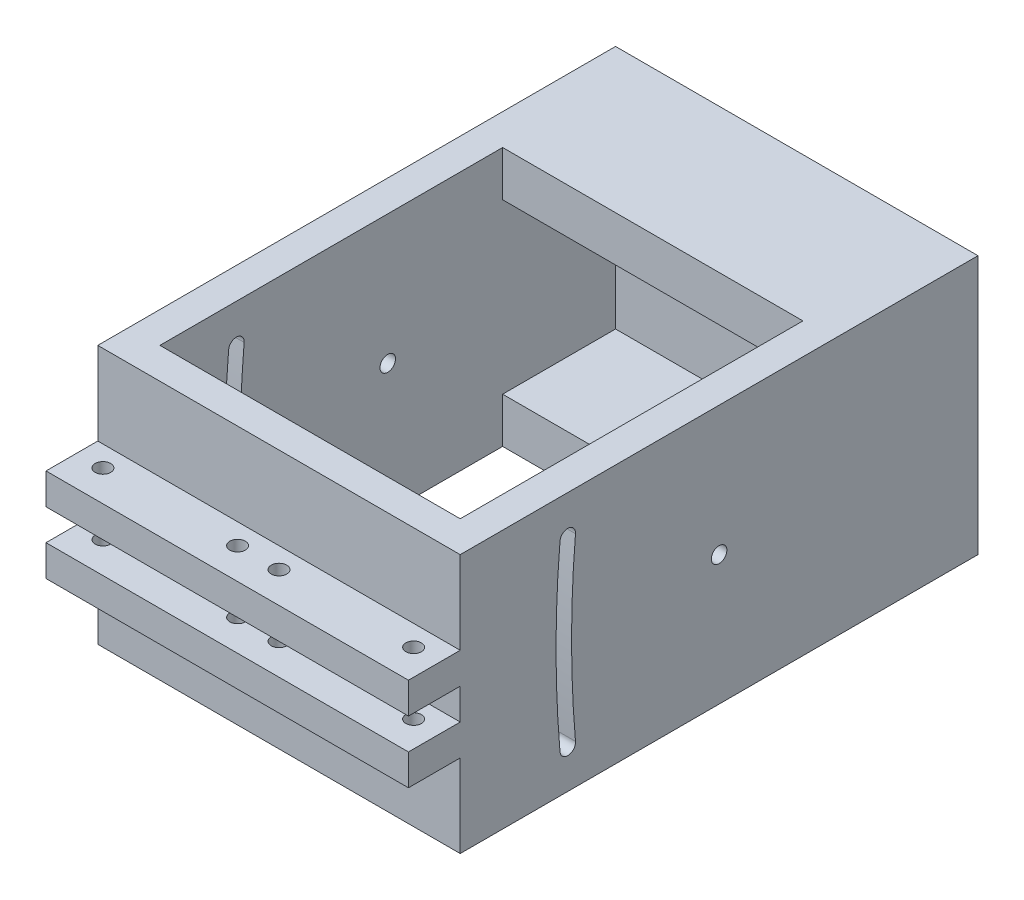
SolidWorks part; units mm, degrees
ref_plane "Front Plane" through (0, 0, 0) normal (0, 0, 1) x (1, 0, 0)
ref_plane "Top Plane" through (0, 0, 0) normal (0, 1, 0) x (1, 0, 0)
ref_plane "Right Plane" through (0, 0, 0) normal (1, 0, 0) x (0, 0, -1)
sketch "Sketch1" plane through (0, 0, 0) normal (0, 1, 0) x (1, 0, 0)
  line L1 (-35, 48.4099) -> (35, 48.4099)
  line L2 (-35, 48.4099) -> (-35, -51.5901)
  line L3 (-35, -51.5901) -> (35, -51.5901)
  line L4 (35, 48.4099) -> (35, -51.5901)
  line L14 (0, -27.5) -> (0, 27.5) construction
  line L16 (-29, 42.4099) -> (29, 42.4099)
  line L17 (-29, 42.4099) -> (-29, -45.5901)
  line L18 (-29, -45.5901) -> (29, -45.5901)
  line L19 (29, 42.4099) -> (29, -45.5901)
  point P14 (0, -51.5901)
  dimension "D1" = 70
  dimension "D2" = 100
  dimension "D3" = 6
  dimension "D4" = 6
  dimension "D5" = 6
  dimension "D6" = 6
  dimension "D9" = 0
extrude "main_body" add sketch "Sketch1" along normal blind 50
sketch "Sketch2" plane through (35, 0, 0) normal (1, 0, 0) x (0, 0, -1)
  line L0 (-51.5901, 50) -> (-51.5901, 0) construction
  circle A0 centre (-1.5901, 25) radius 1.5
  point P4 (-51.5901, 25)
  dimension "D1" = 3
  dimension "D2" = 0
  dimension "D3" = 50
sketch "Sketch3" plane through (0, 0, 51.5901) normal (0, 0, 1) x (1, 0, 0)
  line L0 (-35, 50) -> (35, 50) construction
  line L1 (35, 50) -> (35, 0) construction
  circle A0 centre (0, 25) radius 1.5
  point P4 (0, 50)
  point P7 (35, 25)
  dimension "D1" = 0
  dimension "D3" = 3
  dimension "D2" = 0
extrude "back_wire_hole" cut sketch "Sketch3" against normal up to next
sketch "Sketch6" plane through (0, 0, -48.4099) normal (0, 0, -1) x (-1, 0, 0)
  line L0 (35, 50) -> (35, 0) construction
  line L1 (-35, 50) -> (35, 50) construction
  circle A0 centre (0, 25) radius 1.5
  point P4 (35, 25)
  point P7 (0, 50)
  dimension "D1" = 0
  dimension "D3" = 3
  dimension "D2" = 0
extrude "front_wire_hole" cut sketch "Sketch6" against normal up to next
sketch "Sketch4" plane through (0, 0, 51.5901) normal (0, 0, 1) x (1, 0, 0)
  line L6 (-35, 50) -> (-35, 0) construction
  line L8 (-35, 34) -> (35, 34)
  line L10 (-35, 34) -> (-35, 28)
  line L12 (-35, 28) -> (35, 28)
  line L13 (35, 34) -> (35, 28)
  line L14 (35, 50) -> (35, 0) construction
  point P8 (-35, 25)
  dimension "D1" = 6
  dimension "D2" = 3
extrude "back_lip" add sketch "Sketch4" along normal blind 10
ref_plane "central_horizontal_plane" [suppressed] through (0, 25, 0) normal (0, 1, 0) x (1, 0, 0)
mirror "back_lip_mirror" about plane through (0, 25, 0) normal (0, 1, 0) of "back_lip"
sketch "Sketch5" plane through (0, 34, 0) normal (0, 1, 0) x (1, 0, 0)
  line L0 (35, -61.5901) -> (-35, -61.5901) construction
  line L1 (35, -51.5901) -> (-35, -51.5901) construction
  line L2 (35, -61.5901) -> (35, -51.5901) construction
  line L3 (0, -61.5901) -> (0, -51.5901) construction
  circle A0 centre (4, -55.5901) radius 1.5
  circle A1 centre (30, -55.5901) radius 1.5
  circle A2 centre (-30, -55.5901) radius 1.5
  circle A3 centre (-4, -55.5901) radius 1.5
  point P4 (0, -61.5901)
  dimension "D1" = 4
  dimension "D3" = 0
  dimension "D5" = 3
  dimension "D6" = 3
  dimension "D2" = 4
  dimension "D4" = 5
extrude "back_lip_holes" cut sketch "Sketch5" against normal through all
extrude "geared_arm_hole" cut sketch "Sketch2" against normal up to next
mirror "geared_arm_hole_mirror" about plane through (0, 0, 0) normal (1, 0, 0) of "geared_arm_hole"
sketch "alignment_sketch" plane through (35, 0, 0) normal (1, 0, 0) x (0, 0, -1)
  line L0 (-1.5901, 25) -> (48.4099, 25) construction
  line L1 (48.4099, 50) -> (48.4099, 0) construction
  line L2 (-1.5901, 25) -> (26.6007, 35.2606) construction
  line L3 (-1.5901, 25) -> (26.6007, 14.7394) construction
  point P5 (26.6007, 35.2606)
  point P8 (26.6007, 14.7394)
  dimension "D2" = 30
  dimension "D1" = 20
ref_axis "top_servo_alignment_axis" through (-55.368, 35.2606, -26.6007) along (1, 0, 0)
ref_axis "bottom_servo_alignment_axis" through (-54.8199, 14.7394, -26.6007) along (1, 0, 0)
sketch "Sketch10" plane through (-29, 0, 0) normal (1, 0, 0) x (0, 0, -1)
  line L0 (-51.5901, 0) -> (48.4099, 0) construction
  line L1 (20.6007, 0) -> (43.6007, 0)
  line L2 (20.6007, 0) -> (20.6007, 8.7394)
  line L3 (20.6007, 8.7394) -> (43.6007, 8.7394)
  line L4 (43.6007, 0) -> (43.6007, 8.7394)
  line L5 (48.4099, 25) -> (47.0508, 25) construction
  line L6 (-1.5901, 25) -> (48.4099, 25) construction
  line L7 (20.6007, 41.2606) -> (43.6007, 41.2606)
  line L8 (43.6007, 50) -> (43.6007, 41.2606)
  line L9 (20.6007, 50) -> (43.6007, 50)
  line L10 (20.6007, 50) -> (20.6007, 41.2606)
  dimension "D1" = 6
  dimension "D2" = 23
  dimension "D3" = 6
extrude "servo_mount_main_extrusion" add sketch "Sketch10" along normal up to surface (58 mm away) up to face at (29, 25, 3.0901)
sketch "Sketch11" plane through (35, 0, 0) normal (1, 0, 0) x (0, 0, -1)
  arc A0 (-30.823, 7.5) -> (-30.823, 42.5) centre (168.4099, 25) cw construction
  arc A1 (-32.3172, 42.6313) -> (-32.3172, 7.3687) centre (168.4099, 25) ccw
  arc A2 (-29.3287, 42.3688) -> (-29.3287, 7.6312) centre (168.4099, 25) ccw
  arc A3 (-29.3287, 42.3688) -> (-32.3172, 42.6313) centre (-30.823, 42.5) ccw
  arc A4 (-32.3172, 7.3687) -> (-29.3287, 7.6312) centre (-30.823, 7.5) ccw
  point P3 (-31.5901, 25)
  dimension "D1" = 1.5
  dimension "D2" = 200
  dimension "D3" = 35
  dimension "D4" = 170
extrude "wing_connection_slot" cut sketch "Sketch11" against normal up to next
mirror "wing_connection_slot_mirror" about plane through (0, 0, 0) normal (1, 0, 0) of "wing_connection_slot"
equation "\"gear_spacing\"= 30mm"
equation "\"D2@alignment_sketch\" = \"gear_spacing\""
equation "\"gear_angle_offset\"= 20deg"
equation "\"D1@alignment_sketch\" = \"gear_angle_offset\""
